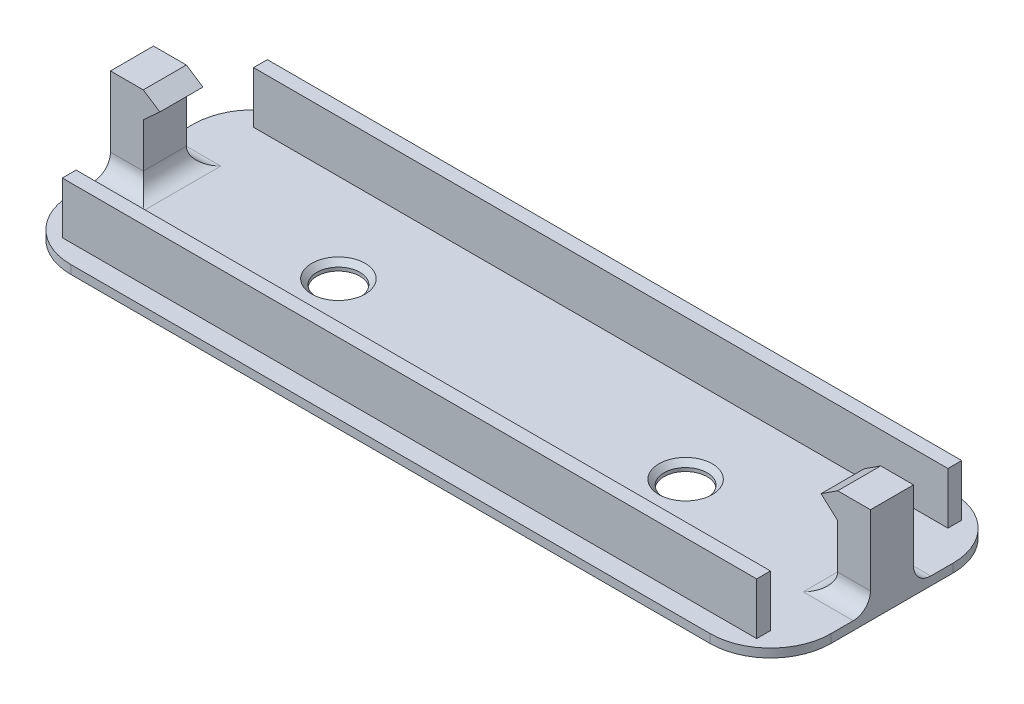
SolidWorks part; units mm, degrees
ref_plane "Front Plane" through (0, 0, 0) normal (0, 0, 1) x (1, 0, 0)
ref_plane "Top Plane" through (0, 0, 0) normal (0, 1, 0) x (1, 0, 0)
ref_plane "Right Plane" through (0, 0, 0) normal (1, 0, 0) x (0, 0, -1)
sketch "Sketch1" plane through (0, 0, 0) normal (0, 1, 0) x (1, 0, 0)
  line L1 (0, 0) -> (80.6, 0)
  line L2 (0, 0) -> (0, 20.6)
  line L3 (0, 20.6) -> (80.6, 20.6)
  line L4 (80.6, 0) -> (80.6, 20.6)
  line L5 (84.41, -3.81) -> (84.41, 24.41)
  line L7 (-3.81, -3.81) -> (-3.81, 24.41)
  line L8 (40.3, 24.41) -> (40.3, -3.81) construction
  line L13 (40.3, 10.3) -> (80.6, 10.3) construction
  line L14 (80.6, 12.8) -> (84.41, 12.8)
  line L15 (80.6, 7.8) -> (84.41, 7.8)
  line L16 (0, 0) -> (0, -1.6)
  line L17 (0, -1.6) -> (80.6, -1.6)
  line L18 (0, 7.8) -> (-3.81, 7.8)
  line L19 (0, 12.8) -> (-3.81, 12.8)
  line L20 (80.6, -1.6) -> (80.6, 0)
  line L21 (80.6, 22.2) -> (80.6, 20.6)
  line L22 (0, 20.6) -> (0, 22.2)
  line L23 (-3.81, -3.8) -> (84.41, -3.8)
  line L24 (-3.81, -3.8) -> (-3.81, 24.4)
  line L25 (-3.81, 24.4) -> (84.41, 24.4)
  line L26 (84.41, -3.8) -> (84.41, 24.4)
  line L27 (0, 22.2) -> (80.6, 22.2)
  line L28 (-3.81, 24.41) -> (84.41, 24.41) construction
  line L29 (-3.81, -3.81) -> (84.41, -3.81) construction
  circle A0 centre (60.45, 10.3) radius 2.5
  circle A1 centre (20.15, 10.3) radius 2.5
  dimension "D7" = 5
  dimension "D1" = 20.6
  dimension "D2" = 80.6
  dimension "D4" = 2.2
  dimension "D5" = 5
  dimension "D6" = 1.6
  dimension "D3" = 3.81
  dimension "D8" = 28.22
extrude "Boss-Extrude1" add sketch "Sketch1" against normal blind 1 contours L24 L25 L7 L23 | L19 L2 L3 L17 L7 | L2 L19 L7 L18 | L1 L2 L18 L7 | L1 L4 L3 L2 A0 A1 | L23 L17 L3 | L25 L1 | L25 L5 L15 L4 L1 | L26 L23 L5 L25 | L3 L4 L14 L5 | L4 L15 L5 L14 | L23 L26 L24 | L26 L25 L24 region at (40.3, 0, -10.3) region at (-0.8898, 0, 0.8) region at (40.3, 0, 0.8) region at (-1.905, 0, -10.3) region at (82.505, 0, -10.3) region at (-1.905, 0, -13.6898) region at (40.3, 0, -21.4)
extrude "Boss-Extrude2" add sketch "Sketch1<3>" along normal blind 10.16 contours L2 L19 L7 L18 | L4 L15 L5 L14 region at (-1.905, 0, -10.3) region at (82.505, 0, -10.3)
sketch "Sketch1<3>" plane through (0, 0, 0) normal (0, 1, 0) x (1, 0, 0) same geometry as "Sketch1"
extrude "Boss-Extrude3" add sketch "Sketch1<4>" along normal blind 6 contours L17 L20 L1 L16 | L27 L22 L3 L21 region at (40.3, 0, 0.8) region at (40.3, 0, -21.4)
sketch "Sketch1<4>" plane through (0, 0, 0) normal (0, 1, 0) x (1, 0, 0) same geometry as "Sketch1"
sketch "Sketch2" plane through (0, 0, -7.8) normal (0, 0, 1) x (1, 0, 0)
  line L0 (0, 10.16) -> (1.9274, 8.905)
  line L1 (1.9274, 8.905) -> (0, 7.16)
  line L2 (0, 10.16) -> (0, 0) construction
  line L3 (0, 7.16) -> (0, 10.16)
  dimension "D1" = 2.3
  dimension "D2" = 2.6
  dimension "D3" = 3
extrude "Boss-Extrude4" add sketch "Sketch2" against normal up to surface (5 mm away) up to face at (-1.905, 5.08, -12.8)
ref_plane "Plane1" through (40.3, 0, 0) normal (-1, 0, 0) x (0, 0, 1)
mirror "Mirror1" about plane through (40.3, 0, 0) normal (-1, 0, 0) of "Boss-Extrude4"
fillet "Fillet1" radius 7 4 edges at (84.41, -0.5, -24.4) (84.41, -0.5, 3.8) (-3.81, -0.5, -24.4) (-3.81, -0.5, 3.8)
fillet "Fillet2" radius 2 6 edges at (80.6, 0, -10.3) (0, 0, -10.3) (82.505, 0, -12.8) (82.505, 0, -7.8) (-1.905, 0, -12.8) (-1.905, 0, -7.8)
chamfer "Chamfer1" distance 0.6 angle 45 2 edges at (60.45, 0, -7.8) (20.15, 0, -7.8)
